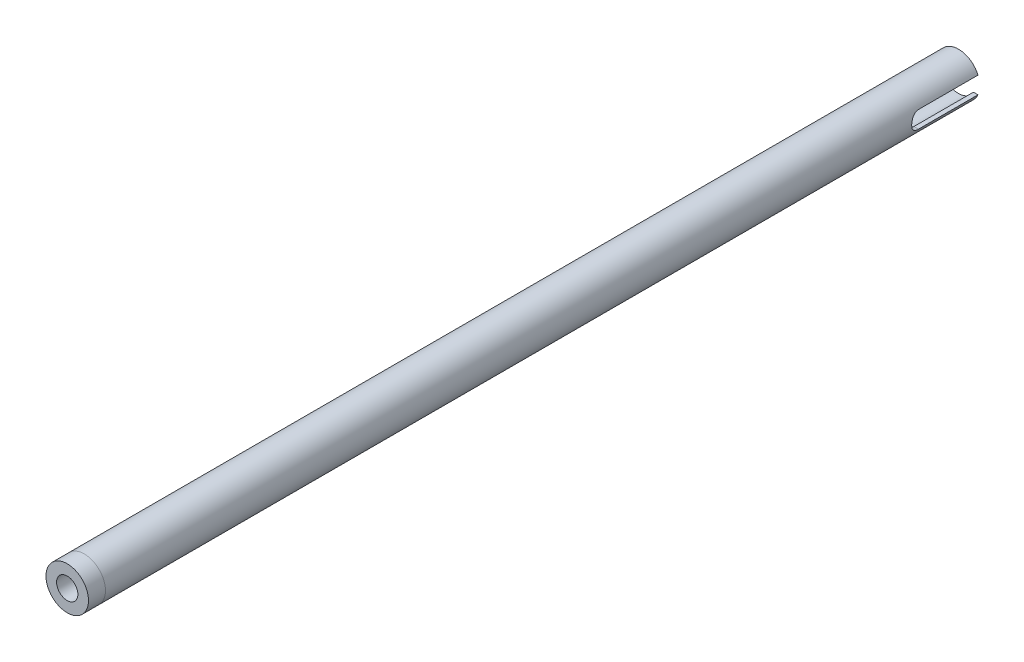
SolidWorks part; units mm, degrees
ref_plane "Front Plane" through (0, 0, 0) normal (0, 0, 1) x (1, 0, 0)
ref_plane "Top Plane" through (0, 0, 0) normal (0, 1, 0) x (1, 0, 0)
ref_plane "Right Plane" through (0, 0, 0) normal (1, 0, 0) x (0, 0, -1)
sketch "Axis" plane through (0, 0, 0) normal (0, 1, 0) x (1, 0, 0)
  line L0 (0, 0) -> (0, 332.6562) construction
  line L1 (0, 0) -> (0, -28.575) construction
  line L2 (0, 332.6562) -> (-7.9375, 332.6562) construction
  line L4 (0, 361.4076) -> (-10.3188, 324.0308) construction
  dimension "D1" = 28.575
  dimension "D2" = 7.9375
sketch "Sketch1" plane through (0, 0, 0) normal (0, 0, 1) x (1, 0, 0)
  line L0 (-7.9375, 0) -> (7.9375, 0) construction
  line L1 (-7.2748, 3.175) -> (7.2748, 3.175)
  line L2 (-7.2748, -3.175) -> (7.2748, -3.175)
  circle A0 centre (0, 0) radius 7.9375
  circle A1 centre (0, 0) radius 6.4135
  circle A2 centre (0, 0) radius 3.9688
  dimension "D1" = 15.875
  dimension "D3" = 7.9375
  dimension "D2" = 1.524
  dimension "D4" = 6.35
extrude "Threaded insert 1-1" add sketch "Sketch1" against normal blind 6.35 contours A2 L1 A1 | A1 L1 A0 | A2 L0 A1 L1 | A1 L0 A0 L1 | L0 A1 L2 A0 | L0 A2 L2 A1 | A2 L2 A1 | A1 L2 A0 | L0 A1 L2 A2 | L0 A0 L2 A1 | A0 L0 A1 L1 | A1 L0 A2 L1 region at (4.7887, 1.6543, 0) region at (4.7887, -1.6543, 0) region at (6.9234, 1.6163, 0) region at (6.9234, -1.6163, 0) region at (-4.7887, -1.6543, 0) region at (-4.7887, 1.6543, 0) region at (0, 4.6159, 0) region at (0, -4.6159, 0) region at (0, 6.5666, 0) region at (6.4237, -3.3281, 0) region at (-6.9234, -1.6163, 0) region at (-6.9234, 1.6163, 0)
extrude "Threaded insert 1-2" add sketch "Sketch1<3>" against normal blind 9.525 from surface contours A2 L1 A1 | A2 L0 A1 L1 | L0 A2 L2 A1 | A2 L2 A1 | L0 A1 L2 A2 | A1 L0 A2 L1 region at (4.7887, 1.6543, 0) region at (4.7887, -1.6543, 0) region at (-4.7887, -1.6543, 0) region at (-4.7887, 1.6543, 0) region at (0, 4.6159, 0) region at (0, -4.6159, 0) starting at face at (7.9375, 0, -6.35)
sketch "Sketch1<3>" plane through (0, 0, 0) normal (0, 0, 1) x (1, 0, 0) same geometry as "Sketch1"
extrude "A-arm tube" add sketch "Sketch1<4>" against normal up to vertex (332.6562 mm away) from surface separate body contours A1 L1 A0 | A1 L0 A0 L1 | L0 A1 L2 A0 | A1 L2 A0 | L0 A0 L2 A1 | A0 L0 A1 L1 region at (6.9234, 1.6163, 0) region at (6.9234, -1.6163, 0) region at (0, 6.5666, 0) region at (6.4237, -3.3281, 0) region at (-6.9234, -1.6163, 0) region at (-6.9234, 1.6163, 0) up to point (0, 0, -332.6562) starting at face at (6.4135, 0, -6.35)
sketch "Sketch1<4>" plane through (0, 0, 0) normal (0, 0, 1) x (1, 0, 0) same geometry as "Sketch1"
extrude "Apex slot" cut sketch "Sketch1<5>" along normal blind 25.4 from surface contours A0 L0 A1 L1 | L0 A0 L2 A1 | A1 L0 A0 L1 | L0 A1 L2 A0 region at (6.9234, 1.6163, 0) region at (6.9234, -1.6163, 0) region at (-6.9234, -1.6163, 0) region at (-6.9234, 1.6163, 0) starting at face at (6.4135, 0, -332.6562)
sketch "Sketch1<5>" plane through (0, 0, 0) normal (0, 0, 1) x (1, 0, 0) same geometry as "Sketch1"
fillet "Fillet1" radius 3.175 4 edges at (-6.4237, 3.175, -307.2562) (-6.4237, -3.175, -307.2562) (6.4237, -3.175, -307.2562) (6.4237, 3.175, -307.2562)
equation "\"tube diameter\"= 5 / 8"
equation "\"tube thickness\"= .06"
equation "\"apex thickness\"= .25"
equation "\"tube slot\"= 1"
equation "\"D1@Sketch1\"=\"tube diameter\""
equation "\"D2@Sketch1\"=\"tube thickness\""
equation "\"threaded insert hole\"= .3125"
equation "\"D3@Sketch1\"=\"threaded insert hole\""
equation "\"D4@Sketch1\"=\"apex thickness\""
equation "\"D1@Apex slot\" = \"tube slot\""
equation "\"D1@Fillet1\"=\"apex thickness\"/2"
equation "\"D2@Axis\"=\"tube diameter\"/2"
